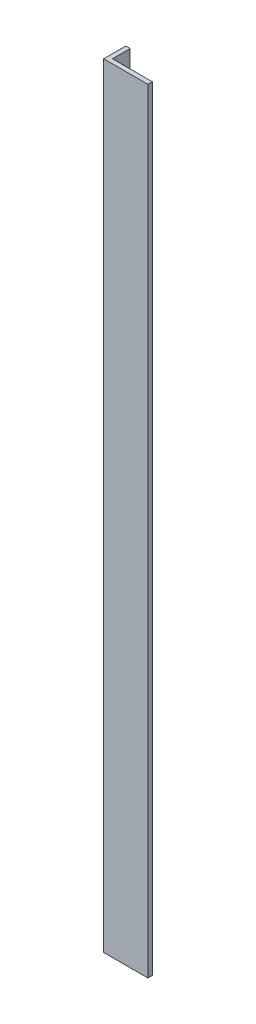
SolidWorks part; units mm, degrees
ref_plane "Front Plane" through (0, 0, 0) normal (0, 0, 1) x (1, 0, 0)
ref_plane "Top Plane" through (0, 0, 0) normal (0, 1, 0) x (1, 0, 0)
ref_plane "Right Plane" through (0, 0, 0) normal (1, 0, 0) x (0, 0, -1)
sketch "Sketch1" plane through (0, 0, 0) normal (0, 1, 0) x (1, 0, 0)
  line L0 (0, 0) -> (0, 10)
  line L1 (0, 10) -> (2, 10)
  line L2 (2, 10) -> (2, 2)
  line L3 (2, 2) -> (20, 2)
  line L4 (20, 2) -> (20, 0)
  line L5 (20, 0) -> (0, 0)
extrude "Boss-Extrude1" add sketch "Sketch1" along normal blind 350
hole_wizard "Ø3.0 (3) Diameter Hole1" positions "Sketch2" profile "Sketch3" hole size "Ø3.0" standard "ISO" end condition through all
sketch "Sketch2" plane through (2, 361.4076, -188.68) normal (1, 0, 0) x (0, 0, 1)
  point P0 (182.68, 355.4076)
  point P1 (182.68, 341.4076)
sketch "Sketch3" plane through (2, 6, -6) normal (0, 1, 0) x (0, 0, -1)
  line L0 (0, 0) -> (0, 2)
  line L1 (0, 2) -> (1.5, 2)
  line L2 (1.5, 2) -> (1.5, 0)
  line L3 (1.5, 0) -> (0, 0)
  line L4 (0, -6.35) -> (0, 107.95) construction
  dimension "Thru Hole Dia." = 3
  dimension "Thru Hole Depth" = 2
hole_wizard "Ø3.0 (3) Diameter Hole2" positions "Sketch4" profile "Sketch5" hole size "Ø3.0" standard "ISO" end condition through all
sketch "Sketch4" plane through (2, 361.4076, -188.68) normal (1, 0, 0) x (0, 0, 1)
  point P0 (182.68, 17.4076)
  point P1 (182.68, 31.4076)
sketch "Sketch5" plane through (2, 344, -6) normal (0, 1, 0) x (0, 0, -1)
  line L0 (0, 0) -> (0, 2)
  line L1 (0, 2) -> (1.5, 2)
  line L2 (1.5, 2) -> (1.5, 0)
  line L3 (1.5, 0) -> (0, 0)
  line L4 (0, -6.35) -> (0, 107.95) construction
  dimension "Thru Hole Dia." = 3
  dimension "Thru Hole Depth" = 2
